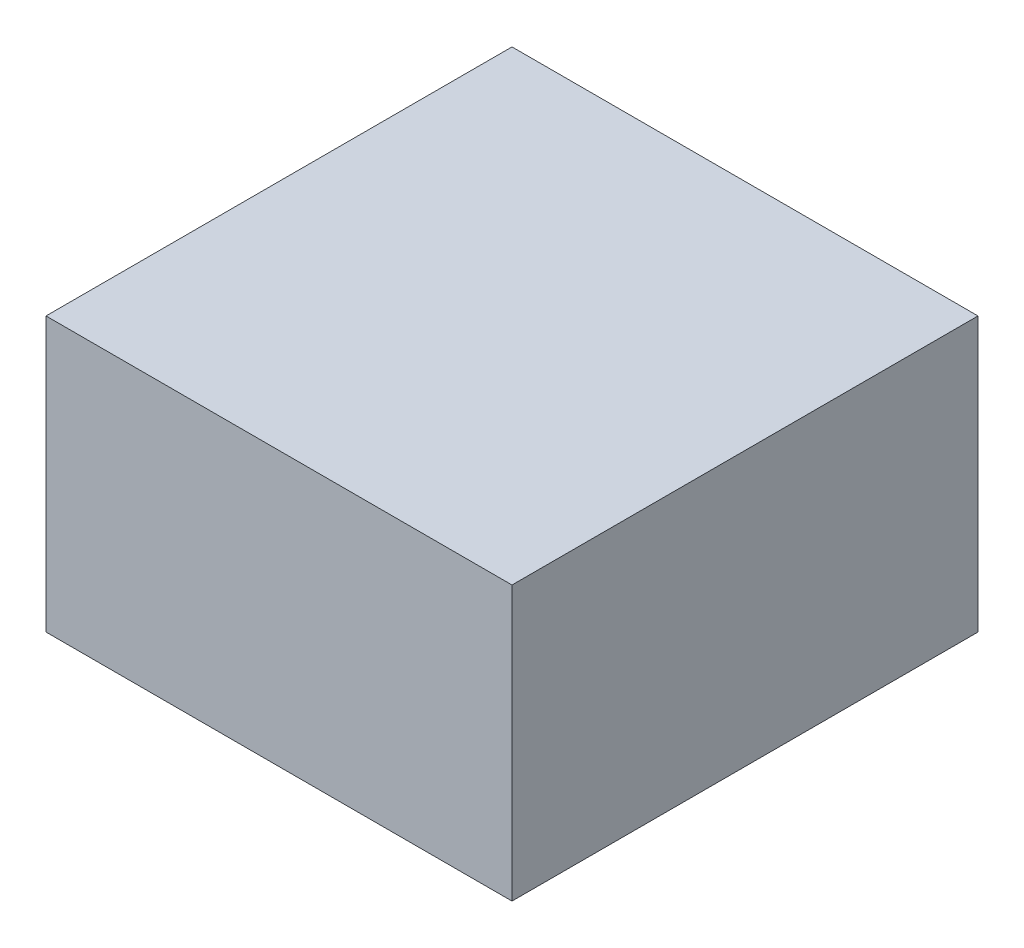
SolidWorks part; units mm, degrees
ref_plane "Front Plane" through (0, 0, 0) normal (0, 0, 1) x (1, 0, 0)
ref_plane "Top Plane" through (0, 0, 0) normal (0, 1, 0) x (1, 0, 0)
ref_plane "Right Plane" through (0, 0, 0) normal (1, 0, 0) x (0, 0, -1)
sketch "Sketch1" plane through (0, 0, 0) normal (0, 1, 0) x (1, 0, 0)
  line L1 (-24, 24) -> (24, 24)
  line L2 (-24, 24) -> (-24, -24)
  line L3 (-24, -24) -> (24, -24)
  line L4 (24, 24) -> (24, -24)
  dimension "D1" = 48
  dimension "D2" = 48
  dimension "D3" = 24
  dimension "D4" = 24
extrude "Boss-Extrude1" add sketch "Sketch1" along normal mid plane 28.2
